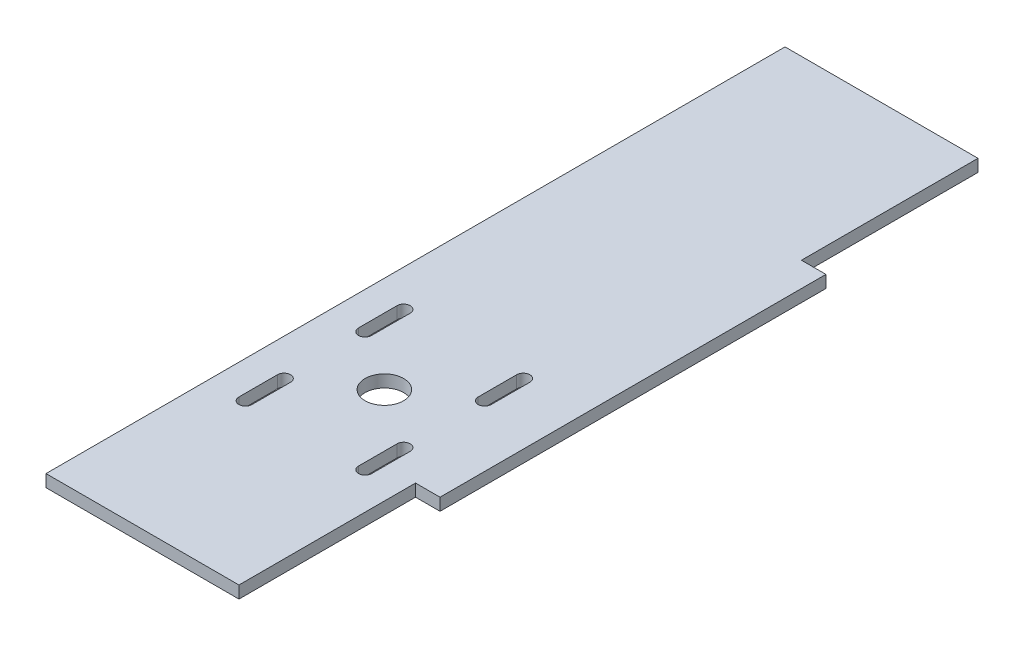
SolidWorks part; units mm, degrees
ref_plane "Front Plane" through (0, 0, 0) normal (0, 0, 1) x (1, 0, 0)
ref_plane "Top Plane" through (0, 0, 0) normal (0, 1, 0) x (1, 0, 0)
ref_plane "Right Plane" through (0, 0, 0) normal (1, 0, 0) x (0, 0, -1)
sketch "Sketch1" plane through (0, 0, 0) normal (0, 1, 0) x (1, 0, 0)
  line L0 (-25, 45.75) -> (25, 45.75)
  line L1 (25, 45.75) -> (25, 0)
  line L2 (25, 0) -> (31.35, 0)
  line L3 (31.35, 0) -> (31.35, -100)
  line L4 (31.35, -100) -> (25, -100)
  line L5 (25, -100) -> (25, -145.75)
  line L6 (25, -145.75) -> (-25, -145.75)
  line L7 (-25, -145.75) -> (-25, -100)
  line L8 (-25, -100) -> (-31.35, -100)
  line L9 (-31.35, -100) -> (-31.35, 0)
  line L10 (-31.35, 0) -> (-25, 0)
  line L11 (-25, 0) -> (-25, 45.75)
  line L12 (-25, 0) -> (-25, -100) construction
  point P11 (0, 45.75)
  point P14 (-31.35, -50)
  dimension "D1" = 6.35
  dimension "D2" = 100
  dimension "D3" = 50
  dimension "D4" = 191.5
extrude "Boss-Extrude1" add sketch "Sketch1" along normal blind 3.175 contours L11 L12 L7 L6 L5 L4 L3 L2 L1 L0 region at (1.7523, 0, 50)
sketch "Sketch3" plane through (0, 3.175, 0) normal (0, 1, 0) x (1, 0, 0)
  line L1 (21.25, -104.325) -> (-21.25, -104.325) construction
  line L2 (21.25, -104.325) -> (21.25, -61.825) construction
  line L3 (21.25, -61.825) -> (-21.25, -61.825) construction
  line L4 (-21.25, -104.325) -> (-21.25, -61.825) construction
  line L5 (21.25, -104.325) -> (-21.25, -61.825) construction
  line L6 (21.25, -61.825) -> (-21.25, -104.325) construction
  line L7 (0, -58.575) -> (0, -107.575) construction
  line L8 (-25, 45.75) -> (25, 45.75) construction
  circle A0 centre (0, -83.075) radius 5
  point P0 (0, -83.075)
  point P5 (0, -62.25)
  point P13 (15.5, -98.575)
  point P14 (-15.5, -98.575)
  point P15 (-15.5, -67.575)
  point P16 (15.5, -67.575)
  dimension "D4" = 10
  dimension "D5" = 49
  dimension "D3" = 42.5
  dimension "D6" = 31
  dimension "D1" = 128.825
extrude "Cut-Extrude1" cut sketch "Sketch3" against normal through all
hole_wizard "M3 Clearance Hole1" positions "Sketch5" profile "Sketch4" hole size "M3" standard "ANSI Metric" end condition through all
sketch "Sketch5" plane through (0, 3.175, 0) normal (0, 1, 0) x (1, 0, 0)
  point P6 (15.5, -98.575)
  point P9 (-15.5, -98.575)
  point P12 (-15.5, -67.575)
  point P15 (15.5, -67.575)
sketch "Sketch4" plane through (15.5, 3.175, 98.575) normal (1, 0, 0) x (0, 0, 1)
  line L0 (0, 0) -> (0, 3.175)
  line L1 (0, 3.175) -> (1.7, 3.175)
  line L2 (1.7, 3.175) -> (1.7, 0)
  line L5 (1.7, 0) -> (0, 0)
  line L11 (0, -6.35) -> (0, 107.95) construction
  dimension "Thru Hole Dia." = 3.4
  dimension "Thru Hole Depth" = 3.175
sketch "Sketch6" plane through (0, 0, 0) normal (0, -1, 0) x (1, 0, 0)
  line L0 (15.5, 103.575) -> (15.5, 93.575) construction
  line L1 (17.2, 103.575) -> (17.2, 93.575)
  line L2 (13.8, 103.575) -> (13.8, 93.575)
  line L3 (-15.5, 103.575) -> (-15.5, 93.575) construction
  line L4 (-13.8, 103.575) -> (-13.8, 93.575)
  line L5 (-17.2, 103.575) -> (-17.2, 93.575)
  line L6 (20.4495, 83.075) -> (-20.4495, 83.075) construction
  line L7 (15.5, 62.575) -> (15.5, 72.575) construction
  line L8 (17.2, 62.575) -> (17.2, 72.575)
  line L9 (13.8, 62.575) -> (13.8, 72.575)
  line L10 (-15.5, 62.575) -> (-15.5, 72.575) construction
  line L11 (-13.8, 62.575) -> (-13.8, 72.575)
  line L12 (-17.2, 62.575) -> (-17.2, 72.575)
  arc A0 (17.2, 103.575) -> (13.8, 103.575) centre (15.5, 103.575) ccw
  arc A1 (13.8, 93.575) -> (17.2, 93.575) centre (15.5, 93.575) ccw
  arc A2 (-13.8, 103.575) -> (-17.2, 103.575) centre (-15.5, 103.575) ccw
  arc A3 (-17.2, 93.575) -> (-13.8, 93.575) centre (-15.5, 93.575) ccw
  circle A5 centre (0, 83.075) radius 5 construction
  circle A6 centre (-15.5, 98.575) radius 1.7 construction
  circle A7 centre (15.5, 98.575) radius 1.7 construction
  arc A8 (17.2, 62.575) -> (13.8, 62.575) centre (15.5, 62.575) cw
  arc A9 (13.8, 72.575) -> (17.2, 72.575) centre (15.5, 72.575) cw
  arc A10 (-13.8, 62.575) -> (-17.2, 62.575) centre (-15.5, 62.575) cw
  arc A11 (-17.2, 72.575) -> (-13.8, 72.575) centre (-15.5, 72.575) cw
  point P2 (15.5, 98.575)
  point P10 (-15.5, 98.575)
  point P20 (0, 83.075)
  point P27 (15.5, 67.575)
  point P34 (-15.5, 67.575)
  dimension "D1" = 10
extrude "Cut-Extrude2" cut sketch "Sketch6" against normal through all
equation "\"length\"= 191.5mm"
equation "\"w_mach\" = 50mm"
equation "\"w_tab\"= 100mm"
equation "\"t_wood\"= 0.125in"
equation "\"t_side\"= 0.25in"
equation "\"D1@Sketch1\"=\"t_side\""
equation "\"D2@Sketch1\"=\"w_tab\""
equation "\"D3@Sketch1\"=\"w_mach\""
equation "\"D4@Sketch1\"=\"length\""
equation "\"D1@Boss-Extrude1\"=\"t_wood\""
equation "\"l_motor\"= 42.5mm"
equation "\"l_servo\"= 0"
equation "\"servocenter\"= 6.35mm"
equation "\"servoholes\"= 49mm"
equation "\"dY\"= 144.825mm"
equation "\"in_rad\"= 16mm"
equation "\"D1@Sketch3\"= \"dY\" - \"in_rad\""
equation "\"D5@Sketch3\"= \"servoholes\""
equation "\"D3@Sketch3\"=\"l_motor\""
